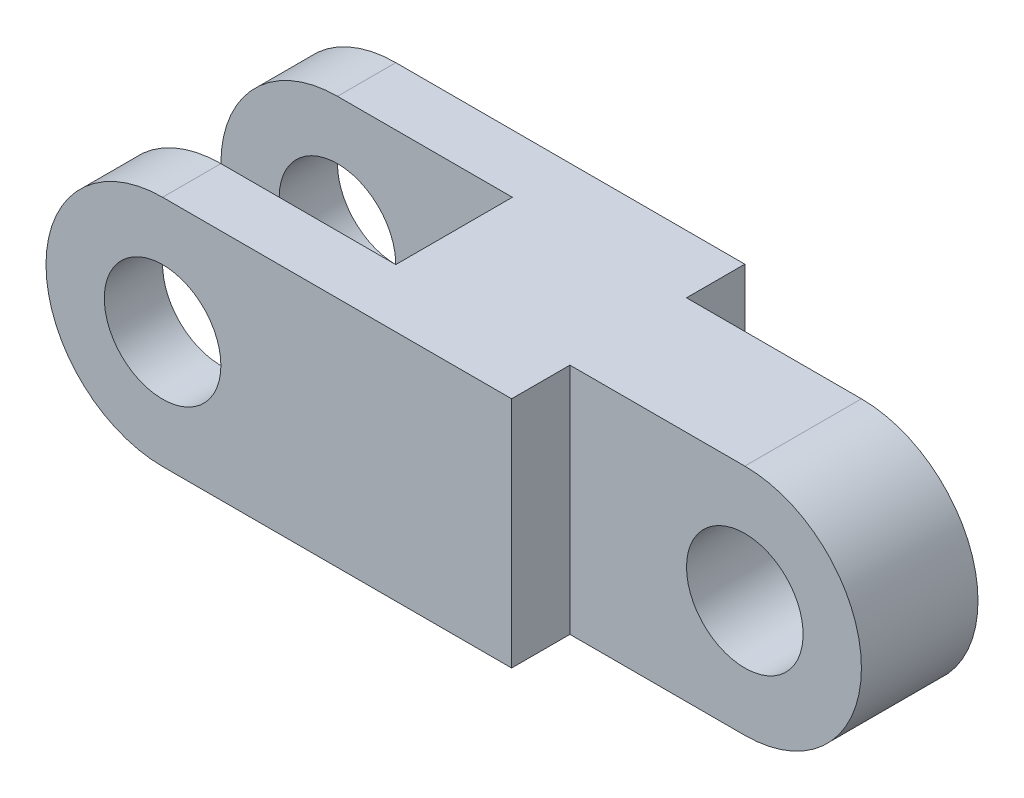
SolidWorks part; units mm, degrees
ref_plane "Front Plane" through (0, 0, 0) normal (0, 0, 1) x (1, 0, 0)
ref_plane "Top Plane" through (0, 0, 0) normal (0, 1, 0) x (1, 0, 0)
ref_plane "Right Plane" through (0, 0, 0) normal (1, 0, 0) x (0, 0, -1)
sketch "Sketch1" plane through (0, 0, 0) normal (0, 0, 1) x (1, 0, 0)
  line L0 (0, 0) -> (44.9358, 0) construction
  line L1 (0, 10) -> (44.9358, 10)
  line L2 (0, -10) -> (44.9358, -10)
  arc A0 (0, 10) -> (0, -10) centre (0, 0) ccw
  arc A1 (44.9358, -10) -> (44.9358, 10) centre (44.9358, 0) ccw
  circle A2 centre (0, 0) radius 5
  circle A3 centre (44.9358, 0) radius 5
  point P3 (22.4679, 0)
  point P12 (70.5001, 0)
  point P13 (52.2959, 0)
  point P14 (30.4011, 0)
  point P15 (44.9358, 0)
  dimension "D1" = 10
  dimension "D2" = 10
  dimension "D3" = 20
extrude "Boss-Extrude1" add sketch "Sketch1" along normal blind 20
sketch "Sketch2" plane through (0, 10, 0) normal (0, 1, 0) x (1, 0, 0)
  line L0 (-10, 0) -> (-10, -20) construction
  line L1 (15, -5) -> (-10, -5)
  line L2 (15, -5) -> (15, -15)
  line L3 (15, -15) -> (-10, -15)
  line L4 (-10, -5) -> (-10, -15)
  line L6 (0, -20) -> (0, 0) construction
  line L7 (54.9358, 0) -> (29.9358, 0)
  line L8 (54.9358, 0) -> (54.9358, -5)
  line L9 (54.9358, -5) -> (29.9358, -5)
  line L10 (29.9358, 0) -> (29.9358, -5)
  line L11 (54.9358, -20) -> (29.9358, -20)
  line L12 (54.9358, -20) -> (54.9358, -15)
  line L13 (54.9358, -15) -> (29.9358, -15)
  line L14 (29.9358, -20) -> (29.9358, -15)
  point P7 (-10, -10)
  point P10 (0, -10)
  dimension "D1" = 10
  dimension "D2" = 25
extrude "Cut-Extrude1" cut sketch "Sketch2" against normal through all
